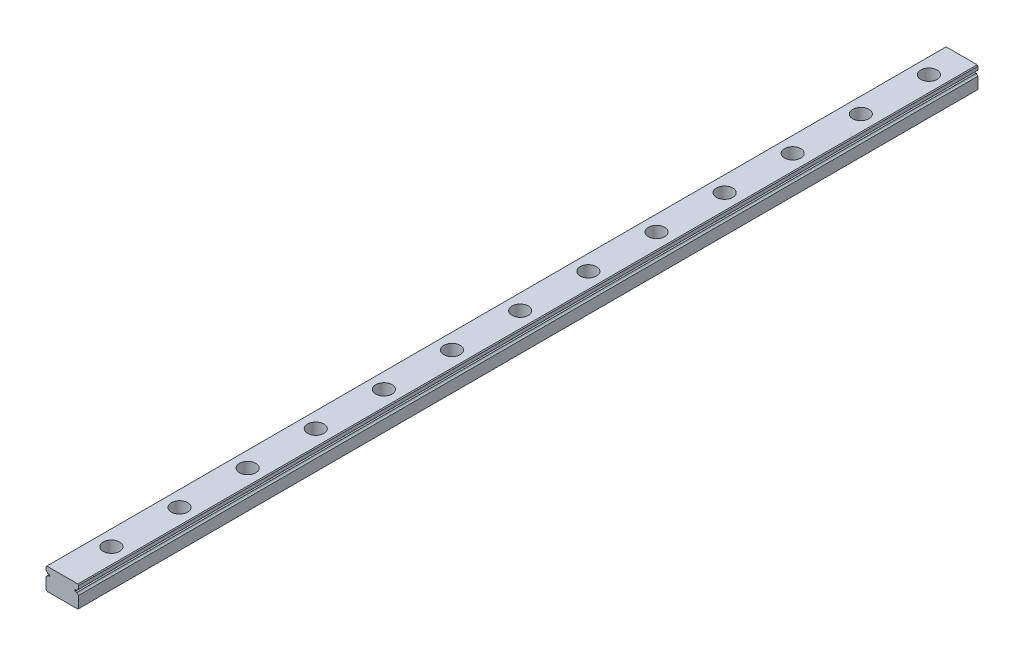
SolidWorks part; units mm, degrees
ref_plane "Спереди" through (0, 0, 0) normal (0, 0, 1) x (1, 0, 0)
ref_plane "Сверху" through (0, 0, 0) normal (0, 1, 0) x (1, 0, 0)
ref_plane "Справа" through (0, 0, 0) normal (1, 0, 0) x (0, 0, -1)
sketch "Эскиз1" plane through (0, 0, 0) normal (0, 0, 1) x (1, 0, 0)
  line L0 (-6, 3.7) -> (-5.7, 4)
  line L1 (-5.7, -4) -> (5.7, -4)
  line L2 (-6, -3.7) -> (-6, 0.549)
  line L3 (-5.7, 4) -> (5.7, 4)
  line L4 (6, -3.7) -> (6, 0.549)
  line L5 (-6, -4) -> (6, 4) construction
  line L6 (-6, 4) -> (6, -4) construction
  line L7 (-6, -3.7) -> (-5.7, -4)
  line L8 (5.7, -4) -> (6, -3.7)
  line L9 (5.7, 4) -> (6, 3.7)
  line L10 (-6, 2.451) -> (-6, 3.7)
  line L11 (-5.3546, 1.7981) -> (-4.6435, 1.7981)
  line L12 (0, 5.4188) -> (0, -5.747) construction
  line L13 (-5.3546, 1.2019) -> (-4.6435, 1.2019)
  line L14 (-4.6435, 1.7981) -> (-4.6435, 1.2019)
  line L15 (4.6435, 1.7981) -> (4.6435, 1.2019)
  line L16 (5.3546, 1.2019) -> (4.6435, 1.2019)
  line L17 (5.3546, 1.7981) -> (4.6435, 1.7981)
  line L18 (6, 2.451) -> (6, 3.7)
  line L19 (4.6435, 1.7981) -> (5.3546, 1.7981) construction
  arc A0 (-6, 0.549) -> (-5.3546, 1.2019) centre (-6.3091, 1.5) ccw
  arc A1 (-5.3546, 1.7981) -> (-6, 2.451) centre (-6.3091, 1.5) ccw
  arc A2 (5.3546, 1.7981) -> (6, 2.451) centre (6.3091, 1.5) cw
  arc A3 (6, 0.549) -> (5.3546, 1.2019) centre (6.3091, 1.5) cw
  point P0 (0, 0)
extrude "Бобышка-Вытянуть1" add sketch "Эскиз1" along normal blind 330
sketch "Эскиз2" plane through (0, 4, 0) normal (0, 1, 0) x (1, 0, 0)
  line L0 (0, 0) -> (0, -26.2396) construction
  line L1 (5.7, 0) -> (-5.7, 0) construction
  line L2 (-3.8306, -12) -> (3.8306, -12) construction
  circle A0 centre (0, -12) radius 3
  circle A1 centre (0, -12) radius 1.75
  dimension "D2" = 3.5
  dimension "D3" = 6
  dimension "D1" = 12
extrude "Вырез-Вытянуть1" cut sketch "Эскиз2" against normal blind 4.5
extrude "Вырез-Вытянуть2" cut sketch "Эскиз2<2>" against normal through all contours A1 region at (0, 4, 12)
sketch "Эскиз2<2>" plane through (0, 4, 0) normal (0, 1, 0) x (1, 0, 0) same geometry as "Эскиз2"
pattern_linear "Линейный массив1" count 16 spacing 25 along (0, 0, 1) of "Вырез-Вытянуть1", "Вырез-Вытянуть2"
